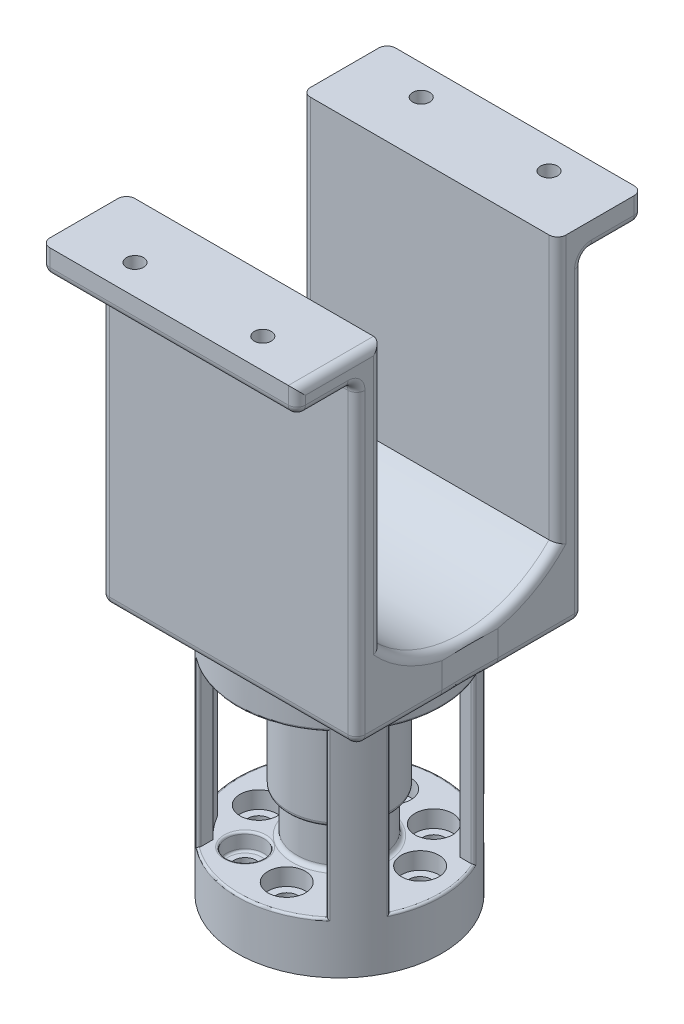
SolidWorks part; units mm, degrees
ref_plane "Front Plane" through (0, 0, 0) normal (0, 0, 1) x (1, 0, 0)
ref_plane "Top Plane" through (0, 0, 0) normal (0, 1, 0) x (1, 0, 0)
ref_plane "Right Plane" through (0, 0, 0) normal (1, 0, 0) x (0, 0, -1)
sketch "Sketch2" plane through (0, 0, 0) normal (0, 1, 0) x (1, 0, 0)
  line L1 (0, 0) -> (30, 0)
  line L2 (0, 0) -> (0, 26.6)
  line L3 (0, 26.6) -> (30, 26.6)
  line L4 (30, 0) -> (30, 26.6)
  dimension "D1" = 26.6
  dimension "D2" = 30
extrude "Boss-Extrude1" add sketch "Sketch2" along normal blind 25
sketch "Sketch4" plane through (0, 25, 0) normal (0, 1, 0) x (1, 0, 0)
  line L0 (30, 0) -> (30, 26.6) construction
  line L1 (0, 26.6) -> (30, 26.6)
  line L2 (0, 26.6) -> (0, 23.6)
  line L3 (0, 23.6) -> (30, 23.6)
  line L4 (30, 26.6) -> (30, 23.6)
  dimension "D1" = 3
extrude "Boss-Extrude2" add sketch "Sketch4" along normal blind 31
sketch "Sketch5" plane through (0, 0, -26.6) normal (0, 0, -1) x (-1, 0, 0)
  line L0 (0, 56) -> (0, 0) construction
  line L1 (-30, 56) -> (0, 56)
  line L2 (-30, 56) -> (-30, 53)
  line L3 (-30, 53) -> (0, 53)
  line L4 (0, 56) -> (0, 53)
  dimension "D1" = 3
extrude "Boss-Extrude3" add sketch "Sketch5" along normal blind 7
ref_plane "Plane1" through (0, 0, -13.3) normal (0, 0, 1) x (1, 0, 0)
hole_wizard "Ø2.0 (2) Diameter Hole1" positions "Sketch8" profile "Sketch9" hole size "Ø2.0" standard "ANSI Metric" end condition through all
sketch "Sketch8" plane through (0, 53, 0) normal (0, -1, 0) x (-1, 0, 0)
  line L3 (-22.5, 30.1) -> (-7.5, 30.1) construction
  line L6 (-30, 26.6) -> (0, 26.6) construction
  line L8 (-30, 33.6) -> (0, 33.6) construction
  line L9 (-30, 33.6) -> (-30, 26.6) construction
  line L10 (0, 33.6) -> (0, 26.6) construction
  line L13 (-15, 33.6) -> (-15, 26.6) construction
  line L14 (-30, 33.6) -> (0, 33.6) construction
  point P0 (-22.5, 30.1)
  point P2 (-7.5, 30.1)
  point P27 (-15, 26.6)
  point P28 (-15, 30.1)
  point P45 (-15, 30.1)
  dimension "D2" = 15
sketch "Sketch9" plane through (22.5, 53, -30.1) normal (1, 0, 0) x (0, 0, -1)
  line L0 (0, 0) -> (0, 3)
  line L1 (0, 3) -> (1, 3)
  line L2 (1, 3) -> (1, 0)
  line L5 (1, 0) -> (0, 0)
  line L11 (0, -6.35) -> (0, 107.95) construction
  dimension "Thru Hole Dia." = 2
  dimension "Thru Hole Depth" = 3
mirror "Mirror2" about plane through (0, 0, -13.3) normal (0, 0, 1) of "Ø2.0 (2) Diameter Hole1", "Boss-Extrude3", "Boss-Extrude2"
sketch "Sketch10" plane through (0, 0, 0) normal (0, -1, 0) x (1, 0, 0)
  line L0 (30, 0) -> (0, 0) construction
  line L1 (25.1, -3.2) -> (4.9, -3.2)
  line L2 (25.1, -3.2) -> (25.1, -23.4)
  line L3 (25.1, -23.4) -> (4.9, -23.4)
  line L4 (4.9, -3.2) -> (4.9, -23.4)
  line L5 (25.1, -3.2) -> (4.9, -23.4) construction
  line L6 (25.1, -23.4) -> (4.9, -3.2) construction
  line L7 (0, -26.6) -> (0, 0) construction
  point P0 (15, -13.3)
  point P8 (15, 0)
  point P11 (0, -13.3)
  dimension "D1" = 20.2
  dimension "D2" = 20.2
extrude "Cut-Extrude1" cut sketch "Sketch10" against normal blind 20
hole_wizard "Ø5.0 (5) Diameter Hole1" positions "Sketch12" profile "Sketch13" hole size "Ø5.0" standard "ANSI Metric" end condition through all
sketch "Sketch12" plane through (0, 0, -26.6) normal (0, 0, -1) x (-1, 0, 0)
  line L1 (0, 10) -> (-30, 10) construction
  line L6 (-30, 0) -> (0, 0) construction
  line L7 (0, 53) -> (0, 0) construction
  line L8 (-30, 53) -> (-30, 0) construction
  point P0 (-15, 10)
  point P18 (-15, 10)
  dimension "D1" = 10
sketch "Sketch13" plane through (15, 10, -26.6) normal (1, 0, 0) x (0, 1, 0)
  line L0 (0, 0) -> (0, 33.6)
  line L1 (0, 33.6) -> (2.5, 33.6)
  line L2 (2.5, 33.6) -> (2.5, 0)
  line L5 (2.5, 0) -> (0, 0)
  line L11 (0, -6.35) -> (0, 107.95) construction
  dimension "Thru Hole Dia." = 5
  dimension "Thru Hole Depth" = 33.6
hole_wizard "Ø5.0 (5) Diameter Hole2" positions "Sketch17" profile "Sketch18" hole size "Ø5.0" standard "ANSI Metric" end condition through all
sketch "Sketch17" plane through (30, 0, 0) normal (1, 0, 0) x (0, 0, -1)
  line L0 (0, 0) -> (26.6, 0) construction
  point P0 (13.3, 10)
  point P5 (13.3, 0)
  dimension "D1" = 10
sketch "Sketch18" plane through (30, 10, -13.3) normal (0, 1, 0) x (0, 0, -1)
  line L0 (0, 0) -> (0, 30)
  line L1 (0, 30) -> (2.5, 30)
  line L2 (2.5, 30) -> (2.5, 0)
  line L5 (2.5, 0) -> (0, 0)
  line L11 (0, -6.35) -> (0, 107.95) construction
  dimension "Thru Hole Dia." = 5
  dimension "Thru Hole Depth" = 30
sketch "Sketch14" plane through (30, 0, 0) normal (1, 0, 0) x (0, 0, -1)
  line L0 (3, 35) -> (23.6, 35) construction
  line L3 (3, 56) -> (3, 25) construction
  line L4 (23.6, 56) -> (23.6, 25) construction
  line L5 (3, 25) -> (23.6, 25) construction
  line L6 (3, 25) -> (23.6, 25)
  arc A0 (3, 25) -> (23.6, 25) centre (13.3, 35) ccw
  dimension "D1" = 10
extrude "Cut-Extrude2" cut sketch "Sketch14" against normal through all
fillet "Fillet1" radius 1 31 edges at (15, 53, 7) (15, 53, -33.6) (30, 20.6442, -13.3) (0, 20.6442, -13.3) (4.9, 0, -13.3) (15, 0, -23.4) (25.1, 0, -13.3) (15, 0, -3.2) (15, 53, 0) (30, 54.5, 7) (0, 54.5, 7) (30, 53, 3.5) (0, 53, 3.5) (30, 56, 2) (0, 40.5, -3) (30, 40.5, -3) (15, 53, -26.6) (30, 54.5, -33.6) (0, 54.5, -33.6) (0, 53, -30.1) (30, 53, -30.1) (30, 40.5, -23.6) (0, 40.5, -23.6) (30, 0, -13.3) (15, 0, -26.6) (0, 26.5, -26.6) (30, 26.5, -26.6) (30, 26.5, 0) (0, 26.5, 0) (15, 0, 0) (0, 0, -13.3)
sketch "Sketch21" plane through (0, 0, 0) normal (0, -1, 0) x (1, 0, 0)
  line L0 (0, -25.6) -> (0, -27.6) construction
  line L1 (0, -26.6) -> (30, -26.6)
  line L2 (0, -26.6) -> (0, 0)
  line L3 (0, 0) -> (30, 0)
  line L4 (30, -26.6) -> (30, 0)
  line L5 (30, -1) -> (30, 1) construction
  line L6 (1, 0) -> (29, 0) construction
  line L7 (29, -26.6) -> (1, -26.6) construction
extrude "Cut-Extrude3" cut sketch "Sketch21" against normal up to surface (20 mm away) up to face at (15, 20, -13.3)
sketch "Sketch22" plane through (0, 20, 0) normal (0, -1, 0) x (1, 0, 0)
  line L6 (30, -25.6) -> (30, -16.5866)
  line L7 (30, -10.0134) -> (30, -1)
  line L8 (29, 0) -> (1, 0)
  line L9 (0, -1) -> (0, -10.0134)
  line L10 (0, -16.5866) -> (0, -25.6)
  line L11 (1, -26.6) -> (29, -26.6)
  line L12 (30, -25.6) -> (30, -16.5866)
  line L13 (30, -10.0134) -> (30, -1)
  line L14 (29, 0) -> (1, 0)
  line L15 (0, -1) -> (0, -10.0134)
  line L16 (0, -16.5866) -> (0, -25.6)
  line L17 (1, -26.6) -> (29, -26.6)
  arc A4 (29, -26.6) -> (30, -25.6) centre (29, -25.6) ccw
  arc A5 (30, -1) -> (29, 0) centre (29, -1) ccw
  arc A6 (1, 0) -> (0, -1) centre (1, -1) ccw
  arc A7 (0, -25.6) -> (1, -26.6) centre (1, -25.6) ccw
  arc A8 (29, -26.6) -> (30, -25.6) centre (29, -25.6) ccw
  arc A9 (30, -1) -> (29, 0) centre (29, -1) ccw
  arc A10 (1, 0) -> (0, -1) centre (1, -1) ccw
  arc A11 (0, -25.6) -> (1, -26.6) centre (1, -25.6) ccw
  spline S2 degree 3 poles (-2968.5933, 47.0705) (39.4956, -71.4078) (30.8064, -42.9313) (29.9478, -14.4067) (29.9348, -13.8616) (29.9345, -13.1798) (29.9352, -13.0409) (29.9379, -12.7656) (29.9399, -12.6279) (29.9478, -12.215) (29.9555, -11.9397) (30.8044, 16.3369) (40.0131, 44.4662) (-2969.183, 17.8449) knots -12.582436 -12.582436 -12.582436 -12.582436 0.25 0.25 0.5 0.5 0.5625 0.5625 0.625 0.625 0.75 0.75 13.467326 13.467326 13.467326 13.467326 only from (30, -16.5866) to (30, -10.0134)
  spline S3 degree 3 poles (2998.5933, -73.6705) (-9.4956, 44.8078) (-0.8064, 16.3313) (0.0522, -12.1933) (0.0652, -12.7384) (0.0655, -13.4202) (0.0648, -13.5591) (0.0621, -13.8344) (0.0601, -13.9721) (0.0522, -14.385) (0.0445, -14.6603) (-0.8044, -42.9369) (-10.0131, -71.0662) (2999.183, -44.4449) knots -12.582436 -12.582436 -12.582436 -12.582436 0.25 0.25 0.5 0.5 0.5625 0.5625 0.625 0.625 0.75 0.75 13.467326 13.467326 13.467326 13.467326 only from (0, -10.0134) to (0, -16.5866)
  spline S4 degree 3 poles (30, -16.5866) (30, -16.0422) (29.9806, -15.4969) (29.9478, -14.4067) (29.9348, -13.8616) (29.9345, -13.1798) (29.9352, -13.0409) (29.9379, -12.7656) (29.9399, -12.6279) (29.9478, -12.215) (29.9555, -11.9397) (29.9802, -11.1141) (30, -10.5636) (30, -10.0134) knots 0 0 0 0 0.25 0.25 0.5 0.5 0.5625 0.5625 0.625 0.625 0.75 0.75 1 1 1 1
  spline S5 degree 3 poles (0, -10.0134) (0, -10.5578) (0.0194, -11.1031) (0.0522, -12.1933) (0.0652, -12.7384) (0.0655, -13.4202) (0.0648, -13.5591) (0.0621, -13.8344) (0.0601, -13.9721) (0.0522, -14.385) (0.0445, -14.6603) (0.0198, -15.4859) (0, -16.0364) (0, -16.5866) knots 0 0 0 0 0.25 0.25 0.5 0.5 0.5625 0.5625 0.625 0.625 0.75 0.75 1 1 1 1
  dimension "D1" = 0
extrude "Boss-Extrude4" add sketch "Sketch22" along normal blind 4
sketch "Sketch26" plane through (0, 16, 0) normal (0, -1, 0) x (1, 0, 0)
  line L0 (29, 0) -> (1, 0) construction
  line L1 (0, -1) -> (0, -10.0134) construction
  circle A0 centre (14.75, -13.25) radius 6
  point P2 (0, 0)
  point P3 (0, 0)
  dimension "D3" = 12
  dimension "D1" = 13.25
  dimension "D2" = 14.75
extrude "Boss-Extrude6" add sketch "Sketch26" along normal blind 18
sketch "Sketch27" plane through (0, -2, 0) normal (0, -1, 0) x (1, 0, 0)
  circle A0 centre (14.75, -13.25) radius 6 construction
  circle A2 centre (14.75, -13.25) radius 5
  dimension "D1" = 10
extrude "Boss-Extrude7" add sketch "Sketch27" along normal blind 5
sketch "Sketch28" plane through (0, -7, 0) normal (0, -1, 0) x (1, 0, 0)
  circle A0 centre (14.75, -13.25) radius 11
  dimension "D1" = 22
extrude "Boss-Extrude8" add sketch "Sketch28" along normal blind 6
hole_wizard "CBORE for M2 SHCS1" positions "Sketch36" profile "Sketch37" counterbore size "M2" standard "ANSI Metric" end condition through all
sketch "Sketch36" plane through (0, -7, 0) normal (0, 1, 0) x (1, 0, 0)
  point P0 (8.0526, 17.6256)
  point P3 (13.1082, 21.0797)
  point P6 (19.1256, 19.9474)
  point P9 (22.5797, 14.8918)
  point P12 (21.4474, 8.8744)
  point P15 (16.3918, 5.4203)
  point P18 (10.3744, 6.5526)
  point P21 (6.9203, 11.6082)
sketch "Sketch37" plane through (8.0526, -7, -17.6256) normal (1, 0, 0) x (0, 0, 1)
  line L0 (0, 0) -> (0, 6)
  line L1 (0, 6) -> (1.3, 6)
  line L3 (1.3, 6) -> (1.3, 2)
  line L4 (1.3, 2) -> (2.2, 2)
  line L5 (2.2, 2) -> (2.2, 0)
  line L7 (2.2, 0) -> (0, 0)
  line L11 (0, -6.35) -> (0, 107.95) construction
  dimension "Thru Hole Dia." = 2.6
  dimension "Thru Hole Depth" = 6
  dimension "C'Bore Dia." = 4.4
  dimension "C'Bore Depth" = 2
fillet "Fillet2" radius 5 1 edges at (14.75, 16, -19.25)
fillet "Fillet3" radius 0.5 3 edges at (14.75, -2, -18.25) (14.75, -7, -18.25) (14.75, -2, -19.25)
sketch "Sketch42" plane through (0, -13, 0) normal (0, -1, 0) x (1, 0, 0)
  circle A0 centre (14.75, -13.25) radius 10.5
  circle A1 centre (14.75, -13.25) radius 11
  circle A2 centre (14.75, -13.25) radius 11
  circle A3 centre (14.75, -13.25) radius 12
  circle M10 centre (14.75, -13.25) radius 11
  dimension "D2" = 21
  dimension "D3" = 24
  dimension "D1" = 0
extrude "Boss-Extrude10" add sketch "Sketch42" against normal up to surface (29 mm away) contours A3 M10 | A3 | A0 region at (3.0894, -13, -13.25) up to face at (14.75, 16, -24.25)
sketch "Sketch44" plane through (0, 0, -26.6) normal (0, 0, -1) x (-1, 0, 0)
  line L0 (-1, 16) -> (-29, 16) construction
  line L1 (-22.25, -7) -> (-7.75, -7)
  line L2 (-22.25, -7) -> (-22.25, 12)
  line L3 (-22.25, 12) -> (-7.75, 12)
  line L4 (-7.75, -7) -> (-7.75, 12)
  line L8 (-1, 16) -> (-1, 52) construction
  line L9 (-29, 52) -> (-29, 16) construction
  line L10 (-26.75, -13) -> (-2.75, -13) construction
  dimension "D1" = 4
  dimension "D2" = 6.75
  dimension "D3" = 6.75
  dimension "D4" = 6
extrude "Cut-Extrude4" cut sketch "Sketch44" against normal blind 6
sketch "Sketch45" plane through (0, 0, 0) normal (0, 0, 1) x (1, 0, 0)
  line L1 (7.75, 12) -> (22.25, 12)
  line L2 (7.75, 12) -> (7.75, -7)
  line L3 (7.75, -7) -> (22.25, -7)
  line L4 (22.25, 12) -> (22.25, -7)
  line L8 (29, 16) -> (1, 16) construction
  line L9 (29, 16) -> (29, 52) construction
  line L10 (1, 52) -> (1, 16) construction
  line L11 (2.75, 16) -> (26.75, 16) construction
  dimension "D1" = 4
  dimension "D2" = 6.75
  dimension "D3" = 6.75
  dimension "D4" = 23
extrude "Cut-Extrude5" cut sketch "Sketch45" against normal blind 6
sketch "Sketch46" plane through (0, 0, 0) normal (-1, 0, 0) x (0, 0, 1)
  line L1 (-18.4968, 12) -> (-8.0032, 12)
  line L2 (-18.4968, 12) -> (-18.4968, -7)
  line L3 (-18.4968, -7) -> (-8.0032, -7)
  line L4 (-8.0032, 12) -> (-8.0032, -7)
  line L8 (-25.25, -13) -> (-1.25, -13) construction
  line L9 (-22.9968, -7) -> (-22.9968, 12) construction
  line L10 (-3.5032, 12) -> (-3.5032, -7) construction
  line L11 (-16.5866, 16) -> (-10.0134, 16) construction
  dimension "D1" = 6
  dimension "D2" = 4.5
  dimension "D3" = 4.5
  dimension "D4" = 4
extrude "Cut-Extrude6" cut sketch "Sketch46" against normal blind 6
sketch "Sketch47" plane through (30, 0, 0) normal (1, 0, 0) x (0, 0, -1)
  line L1 (8.3825, 12) -> (18.1175, 12)
  line L2 (8.3825, 12) -> (8.3825, -7)
  line L3 (8.3825, -7) -> (18.1175, -7)
  line L4 (18.1175, 12) -> (18.1175, -7)
  line L6 (10.0134, 16) -> (16.5866, 16) construction
  line L8 (22.6175, 12) -> (22.6175, -7) construction
  line L9 (3.8825, -7) -> (3.8825, 12) construction
  line L10 (1.25, -13) -> (25.25, -13) construction
  dimension "D1" = 4.5
  dimension "D2" = 4.5
  dimension "D3" = 4
  dimension "D4" = 6
extrude "Cut-Extrude7" cut sketch "Sketch47" against normal blind 6
fillet "Fillet4" radius 1 12 edges at (0.2929, 16, -0.2929) (15, 16, 0) (29.7071, 16, -0.2929) (29.7071, 16, -26.3071) (15, 16, -26.6) (0.2929, 16, -26.3071)
fillet "Fillet7" radius 0.25 18 edges at (15.0638, -7, -1.2541) (22.25, 2.5, -3.8825) (15.0638, 12, -1.2541) (7.75, 2.5, -3.5032) (2.75, -7, -13.25) (3.9578, 2.5, -8.0032) (2.75, 12, -13.25) (3.9578, 2.5, -18.4968) (15.0638, -7, -25.2459) (7.75, 2.5, -22.9968) (15.0638, 12, -25.2459) (22.25, 2.5, -22.6175) (26.75, -7, -13.25) (25.7185, 2.5, -18.1175) (26.75, 12, -13.25) (25.7185, 2.5, -8.3825) (10.3744, -7, -4.3526) (10.3744, -9, -4.3526)
